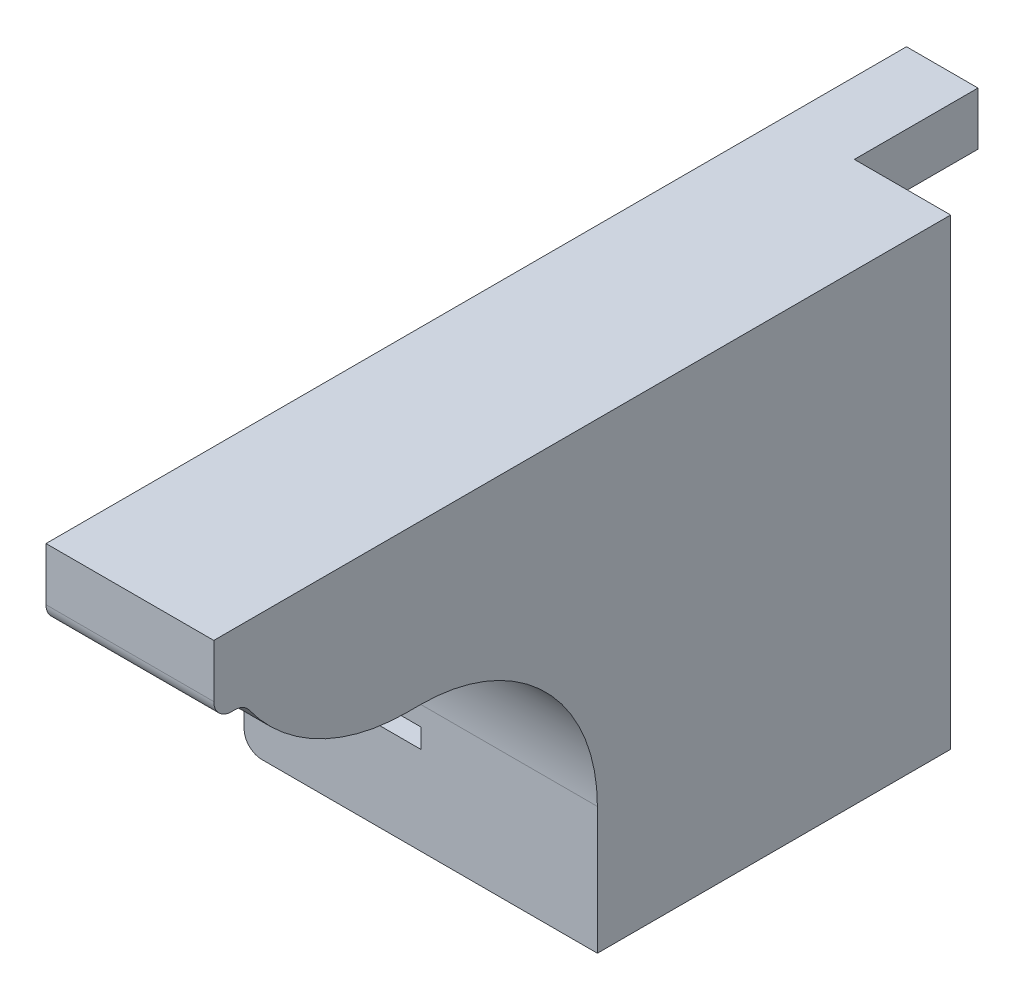
SolidWorks part; units mm, degrees
ref_plane "Front Plane" through (0, 0, 0) normal (0, 0, 1) x (1, 0, 0)
ref_plane "Top Plane" through (0, 0, 0) normal (0, 1, 0) x (1, 0, 0)
ref_plane "Right Plane" through (0, 0, 0) normal (1, 0, 0) x (0, 0, -1)
sketch "Esquisse1" plane through (0, 0, 0) normal (0, 0, 1) x (1, 0, 0)
  line L0 (0, 0) -> (10, 0)
  line L1 (10, 0) -> (10, -22.2)
  line L2 (10, -22.2) -> (-10, -22.2)
  line L3 (-10, -22.2) -> (-10, -17.2)
  line L4 (-10, -17.2) -> (0, -17.2)
  line L5 (0, -17.2) -> (0, -16.1)
  line L6 (0, -16.1) -> (-10, -16.1)
  line L7 (-10, -16.1) -> (-10, -11.1)
  line L8 (-10, -11.1) -> (0, -11.1)
  line L9 (0, -11.1) -> (0, -10)
  line L10 (0, -10) -> (-10, -10)
  line L11 (-10, -10) -> (-10, -5)
  line L12 (-10, -5) -> (0, -5)
  line L13 (0, -5) -> (0, 0)
  dimension "D1" = 10
  dimension "D2" = 10
  dimension "D3" = 1.1
  dimension "D4" = 1.1
  dimension "D5" = 5
  dimension "D6" = 5
  dimension "D7" = 5
  dimension "D8" = 5
extrude "Boss.-Extru.1" add sketch "Esquisse1" along normal blind 10
sketch "Esquisse2" plane through (0, 0, 0) normal (0, 0, -1) x (-1, 0, 0)
  line L0 (10, -22.2) -> (-10, -22.2) construction
  line L1 (-10, 0) -> (-0.5, 0)
  line L2 (-10, 0) -> (-10, -22.2)
  line L3 (-10, -22.2) -> (-0.5, -22.2)
  line L4 (-0.5, 0) -> (-0.5, -22.2)
  dimension "D1" = 9.5
extrude "Boss.-Extru.2" add sketch "Esquisse2" along normal blind 10
sketch "Esquisse3" plane through (0, 0, 10) normal (0, 0, 1) x (1, 0, 0)
  line L1 (10, 0) -> (0, 0)
  line L2 (10, 0) -> (10, -5)
  line L3 (10, -5) -> (0, -5)
  line L4 (0, 0) -> (0, -5)
extrude "Boss.-Extru.3" add sketch "Esquisse3" along normal blind 20
fillet "Congé1" radius 10 1 edges at (5, -5, 10)
chamfer "Chanfrein1" distance 4 angle 45 1 edges at (-10, -5, 5)
fillet "Congé3" radius 1 6 edges at (-10, -9, 5) (-10, -10, 5) (-10, -22.2, 5) (-10, -17.2, 5) (-10, -16.1, 5) (-10, -11.1, 5)
sketch "Esquisse5" plane through (0, 0, 0) normal (0, 1, 0) x (1, 0, 0)
  line L0 (10, -30) -> (10, 10) construction
  line L1 (0.5, 10) -> (10, 10)
  line L2 (0.5, 10) -> (0.5, 5.2815)
  line L3 (0.5, 5.2815) -> (10, 5.2815)
  line L4 (10, 10) -> (10, 5.2815)
extrude "Boss.-Extru.5" add sketch "Esquisse5" along normal blind 4
sketch "Esquisse6" plane through (0, 0, -10) normal (0, 0, -1) x (-1, 0, 0)
  line L1 (-0.5, 4) -> (-4.5489, 4)
  line L2 (-0.5, 4) -> (-0.5, 1)
  line L3 (-0.5, 1) -> (-4.5489, 1)
  line L4 (-4.5489, 4) -> (-4.5489, 1)
  dimension "D1" = 3
extrude "Boss.-Extru.6" add sketch "Esquisse6" along normal blind 7
sketch "Esquisse7" plane through (0, 0, -5.2815) normal (0, 0, 1) x (1, 0, 0)
  line L1 (10, 4) -> (0.5, 4)
  line L2 (10, 4) -> (10, 0)
  line L3 (10, 0) -> (0.5, 0)
  line L4 (0.5, 4) -> (0.5, 0)
extrude "Boss.-Extru.7" add sketch "Esquisse7" along normal blind 37
fillet "Congé4" radius 11 1 edges at (5, -5, 30)
fillet "Congé6" radius 1 2 edges at (5.25, 0, 31.7185) (5.25, 0, 30)
